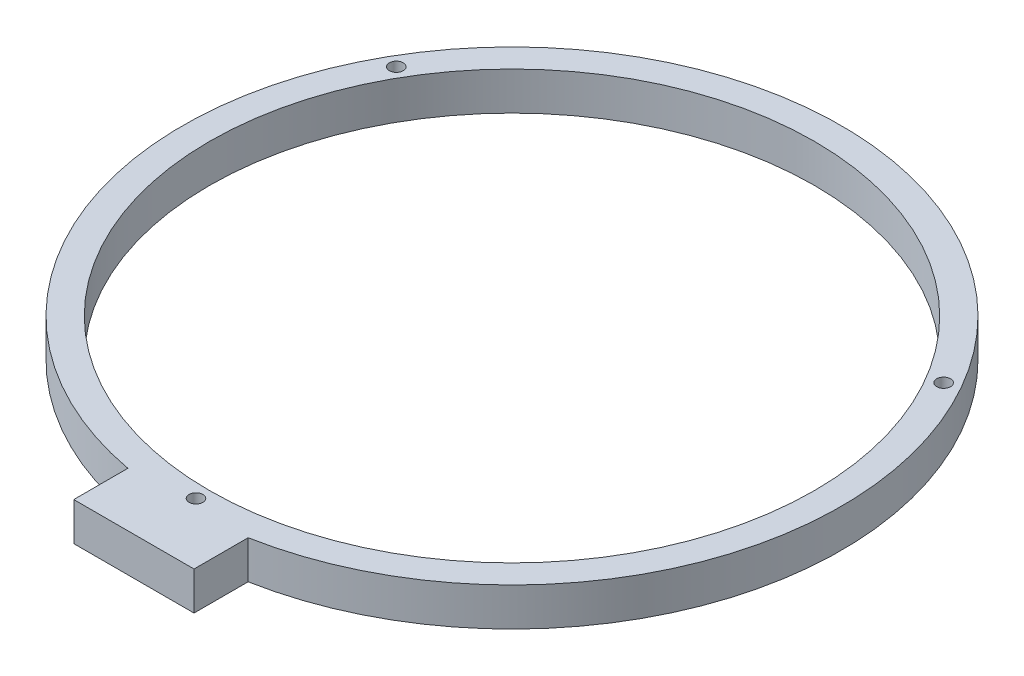
SolidWorks part; units mm, degrees
ref_plane "Front Plane" through (0, 0, 0) normal (0, 0, 1) x (1, 0, 0)
ref_plane "Top Plane" through (0, 0, 0) normal (0, 1, 0) x (1, 0, 0)
ref_plane "Right Plane" through (0, 0, 0) normal (1, 0, 0) x (0, 0, -1)
sketch "Sketch1" plane through (0, 0, 0) normal (0, 1, 0) x (1, 0, 0)
  line L0 (-10, -53.8799) -> (-10, -62.8799)
  line L1 (-10, -62.8799) -> (10, -62.8799)
  line L2 (10, -62.8799) -> (10, -53.8799)
  arc A0 (10, -53.8799) -> (-10, -53.8799) centre (0, 0) ccw
  circle A1 centre (0, 0) radius 50.3
  point P9 (0, -62.8799)
  dimension "D1" = 4.5
  dimension "D2" = 109.6
  dimension "D3" = 20
  dimension "D4" = 9
extrude "Boss-Extrude1" add sketch "Sketch1" along normal blind 6.35
sketch "Sketch2" plane through (0, 6.35, 0) normal (0, 1, 0) x (1, 0, 0)
  line L0 (0, -50.3) -> (0, -54.8) construction
  circle A0 centre (0, 0) radius 50.3 construction
  circle A1 centre (0, 0) radius 54.8 construction
  circle A2 centre (0, -52.55) radius 1.15
  dimension "D1" = 2.3
extrude "Cut-Extrude1" cut sketch "Sketch2" against normal up to next
pattern_circular "CirPattern1" count 3 over 360 about axis through (0, 6.35, 0) along (0, 1, 0) of "Cut-Extrude1"
